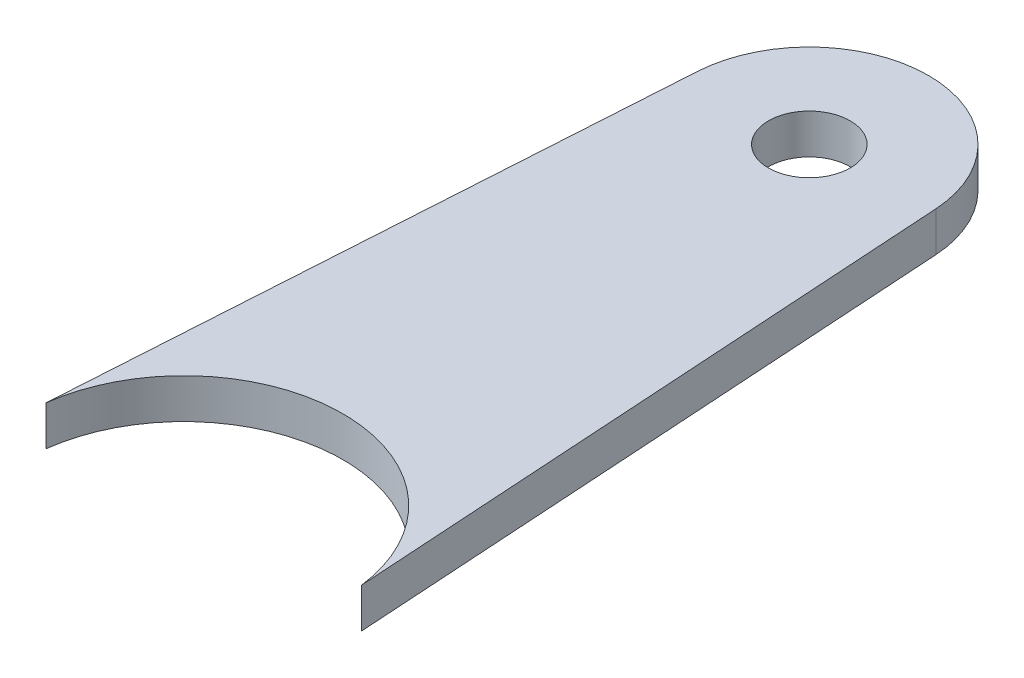
SolidWorks part; units mm, degrees
ref_plane "Front Plane" through (0, 0, 0) normal (0, 0, 1) x (1, 0, 0)
ref_plane "Top Plane" through (0, 0, 0) normal (0, 1, 0) x (1, 0, 0)
ref_plane "Right Plane" through (0, 0, 0) normal (1, 0, 0) x (0, 0, -1)
sketch "Sketch1" plane through (0, 0, 0) normal (0, 1, 0) x (1, 0, 0)
  line L0 (0, 0) -> (3.194, 50.5372)
  line L1 (0, 0) -> (25.4, 0)
  line L2 (25.4, 0) -> (22.206, 50.5372)
  arc A1 (3.194, 50.5372) -> (22.206, 50.5372) centre (12.7, 49.9364) cw
  circle A2 centre (12.7, 49.9364) radius 3.2639
  circle A3 centre (12.7, 0) radius 12.7
  point P9 (12.7, 0)
  dimension "D1" = 6.5278
  dimension "D2" = 49.9364
  dimension "D3" = 9.525
  dimension "D5" = 25.4
  dimension "D4" = 25.4
extrude "Boss-Extrude1" add sketch "Sketch1" along normal blind 3.175 contours A3 L2 A1 L0 A2 region at (12.7, 0, -32.1549)
